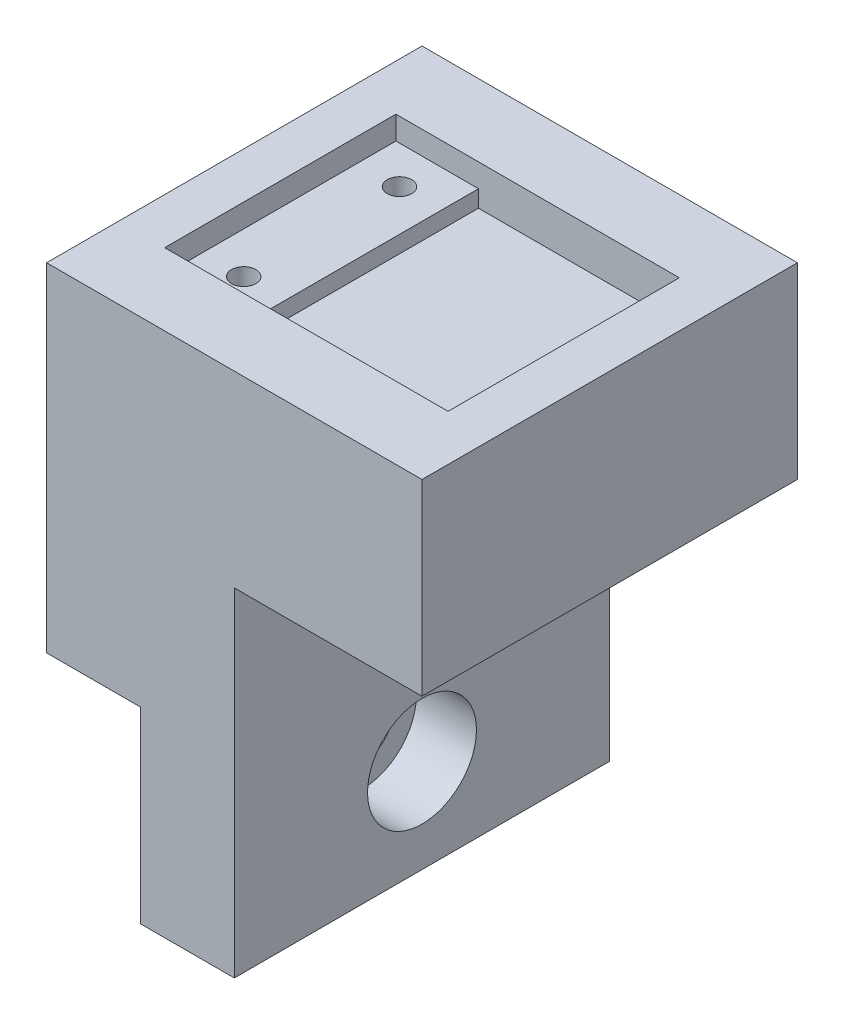
SolidWorks part; units mm, degrees
ref_plane "Front Plane" through (0, 0, 0) normal (0, 0, 1) x (1, 0, 0)
ref_plane "Top Plane" through (0, 0, 0) normal (0, 1, 0) x (1, 0, 0)
ref_plane "Right Plane" through (0, 0, 0) normal (1, 0, 0) x (0, 0, -1)
sketch "Profile" plane through (0, 0, 0) normal (0, 0, 1) x (1, 0, 0)
  line L1 (-6.35, 22.86) -> (6.35, 22.86)
  line L2 (-6.35, 22.86) -> (-6.35, 0)
  line L3 (-6.35, 0) -> (6.35, 0)
  line L4 (6.35, 22.86) -> (6.35, 0)
  line L5 (0, 0) -> (6.35, 0)
  line L6 (0, 0) -> (0, -12.7)
  line L7 (0, -12.7) -> (6.35, -12.7)
  line L8 (6.35, 0) -> (6.35, -12.7)
  dimension "D1" = 22.86
  dimension "D2" = 12.7
  dimension "D3" = 6.35
  dimension "D4" = 12.7
extrude "Boss-Extrude1" add sketch "Profile" along normal mid plane 25.4 contours L4 L1 L2 L3 | L8 L3 L6 L7 region at (0, 11.43, 0) region at (3.175, -6.35, 0)
sketch "ScrewHole" plane through (0, 0, 0) normal (-1, 0, 0) x (0, 0, 1)
  line L0 (12.7, 0) -> (12.7, -12.7) construction
  line L1 (12.7, -12.7) -> (-12.7, -12.7) construction
  circle A0 centre (0, -6.35) radius 2.159
  point P5 (12.7, -6.35)
  point P10 (0, -12.7)
  dimension "D1" = 4.318
extrude "Cut-Extrude1" cut sketch "ScrewHole" against normal through all both
sketch "Sketch3" plane through (6.35, 0, 0) normal (1, 0, 0) x (0, 0, -1)
  circle A0 centre (0, -6.35) radius 2.159 construction
  circle A1 centre (0, -6.35) radius 2.159
  circle A2 centre (0, -6.35) radius 3.683
  dimension "D1" = 7.366
extrude "Cut-Extrude2" cut sketch "Sketch3" against normal blind 4.064
sketch "Sketch4" plane through (6.35, 0, 0) normal (1, 0, 0) x (0, 0, -1)
  line L0 (12.7, 22.86) -> (12.7, -12.7) construction
  line L1 (-12.7, 22.86) -> (12.7, 22.86)
  line L2 (-12.7, 22.86) -> (-12.7, 10.16)
  line L3 (-12.7, 10.16) -> (12.7, 10.16)
  line L4 (12.7, 22.86) -> (12.7, 10.16)
  dimension "D1" = 12.7
extrude "Boss-Extrude2" add sketch "Sketch4" along normal blind 12.7
sketch "Sketch6" plane through (0, 22.86, 0) normal (0, 1, 0) x (1, 0, 0)
  line L0 (-6.35, -12.7) -> (-6.35, 12.7) construction
  line L1 (-3.2385, 7.8232) -> (15.9385, 7.8232)
  line L2 (-3.2385, 7.8232) -> (-3.2385, -7.8232)
  line L3 (-3.2385, -7.8232) -> (15.9385, -7.8232)
  line L4 (15.9385, 7.8232) -> (15.9385, -7.8232)
  line L5 (-6.35, -12.7) -> (19.05, -12.7) construction
  point P6 (-6.35, 0)
  point P7 (-3.2385, 0)
  point P10 (6.35, -12.7)
  point P11 (6.35, -7.8232)
  dimension "D1" = 19.177
  dimension "D2" = 15.6464
extrude "Cut-Extrude3" cut sketch "Sketch6" against normal blind 1.5748
sketch "Sketch7" plane through (0, 21.2852, 0) normal (0, 1, 0) x (1, 0, 0)
  line L0 (13.1445, 5.2705) -> (13.1445, -5.2705) construction
  line L1 (15.9385, -7.8232) -> (15.9385, 7.8232) construction
  line L2 (6.35, 7.8232) -> (6.35, -7.8232) construction
  line L3 (15.9385, 7.8232) -> (-3.2385, 7.8232) construction
  line L4 (-3.2385, -7.8232) -> (15.9385, -7.8232) construction
  circle A0 centre (13.1445, 5.2705) radius 0.8255
  circle A1 centre (13.1445, -5.2705) radius 0.8255
  circle A2 centre (-0.4445, -5.2705) radius 0.8255
  circle A3 centre (-0.4445, 5.2705) radius 0.8255
  point P6 (15.9385, 0)
  point P7 (13.1445, 0)
  dimension "D3" = 1.651
  dimension "D4" = 1.651
  dimension "D1" = 10.541
  dimension "D2" = 2.794
ref_plane "Plane1" through (6.35, 0, 0) normal (1, 0, 0) x (0, 0, -1)
sketch "Sketch9" plane through (0, 21.2852, 0) normal (0, 1, 0) x (1, 0, 0)
  line L0 (-3.2385, -7.8232) -> (15.9385, -7.8232) construction
  line L1 (2.3495, 7.8232) -> (15.9385, 7.8232)
  line L2 (2.3495, 7.8232) -> (2.3495, -7.8232)
  line L3 (2.3495, -7.8232) -> (15.9385, -7.8232)
  line L4 (15.9385, 7.8232) -> (15.9385, -7.8232)
  line L7 (15.9385, -7.8232) -> (15.9385, 7.8232) construction
  line L8 (-3.2385, 7.8232) -> (-3.2385, -7.8232) construction
  line L9 (15.9385, 7.8232) -> (-3.2385, 7.8232) construction
  dimension "D1" = 5.588
extrude "Cut-Extrude5" cut sketch "Sketch9" against normal blind 1.143
extrude "Cut-Extrude6" cut sketch "Sketch7" against normal blind 12.7 contours A2 | A3
